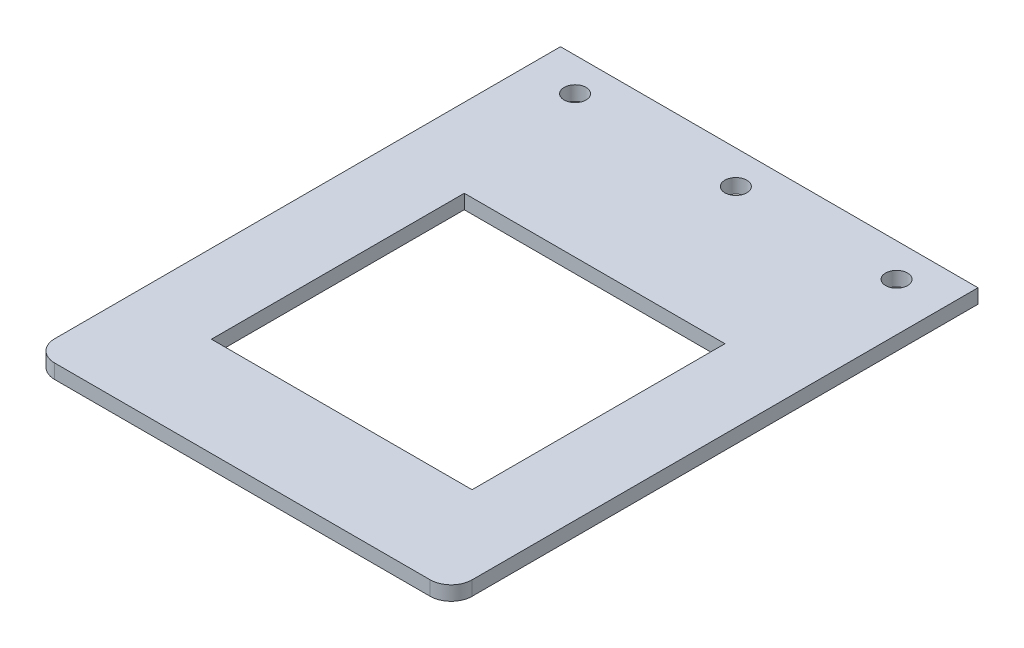
SolidWorks part; units mm, degrees
ref_plane "Front Plane" through (0, 0, 0) normal (0, 0, 1) x (1, 0, 0)
ref_plane "Top Plane" through (0, 0, 0) normal (0, 1, 0) x (1, 0, 0)
ref_plane "Right Plane" through (0, 0, 0) normal (1, 0, 0) x (0, 0, -1)
sketch "Sketch1" plane through (0, 0, 0) normal (0, 1, 0) x (1, 0, 0)
  line L10 (-16.9379, -16.3429) -> (10.3671, -16.3429)
  line L11 (10.3671, -16.3429) -> (10.3671, 10.1491)
  line L12 (10.3671, 10.1491) -> (-16.9379, 10.1491)
  line L13 (-16.9379, 10.1491) -> (-16.9379, -16.3429)
  line L16 (-14.2871, 14.6854) -> (12.9539, 14.6854)
  line L17 (12.9539, 14.6854) -> (12.9539, 18.4324)
  line L18 (12.9539, 18.4324) -> (-14.2871, 18.4324)
  line L19 (-14.2871, 18.4324) -> (-14.2871, 14.6854)
  line L22 (-25.1937, -23.3118) -> (-25.1937, 28.4832)
  line L23 (18.5453, 28.4832) -> (18.5453, -23.3118)
  line L24 (-25.1937, 28.4832) -> (18.5453, 28.4832)
  line L25 (18.5453, -23.3118) -> (18.5453, -24.5118)
  line L26 (-25.1937, -23.3118) -> (-25.1937, -24.5118)
  line L29 (16.3453, -26.7118) -> (-22.9937, -26.7118)
  circle A0 centre (-20.1649, 24.9832) radius 1.15
  circle A1 centre (-3.3249, 24.9832) radius 1.15
  circle A2 centre (13.5151, 24.9832) radius 1.15
  arc A5 (18.5453, -24.5118) -> (16.3453, -26.7118) centre (16.3453, -24.5118) cw
  arc A6 (-25.1937, -24.5118) -> (-22.9937, -26.7118) centre (-22.9937, -24.5118) ccw
extrude "Boss-Extrude1" add sketch "Sketch1" along normal blind 1.5
sketch "Sketch2" plane through (0, 1.5, 0) normal (0, 1, 0) x (1, 0, 0)
  line L0 (-14.2871, 18.4324) -> (12.9539, 18.4324)
  line L1 (12.9539, 18.4324) -> (12.9539, 14.6854)
  line L2 (12.9539, 14.6854) -> (-14.2871, 14.6854)
  line L3 (-14.2871, 14.6854) -> (-14.2871, 18.4324)
  line L4 (18.5453, 28.4832) -> (-25.1937, 28.4832)
  line L5 (-25.1937, 28.4832) -> (-25.1937, -24.5118)
  line L6 (-22.9937, -26.7118) -> (16.3453, -26.7118)
  line L7 (18.5453, -24.5118) -> (18.5453, 28.4832)
  line L8 (18.5453, 28.4832) -> (-25.1937, 28.4832)
  line L9 (-25.1937, 28.4832) -> (-25.1937, -24.5118)
  line L11 (18.5453, -24.5118) -> (18.5453, 28.4832)
  line L16 (-22.9937, -26.7118) -> (16.3453, -26.7118)
  arc A2 (-25.1937, -24.5118) -> (-22.9937, -26.7118) centre (-22.9937, -24.5118) ccw
  arc A3 (-25.1937, -24.5118) -> (-22.9937, -26.7118) centre (-22.9937, -24.5118) ccw
  arc A6 (16.3453, -26.7118) -> (18.5453, -24.5118) centre (16.3453, -24.5118) ccw
  arc A7 (16.3453, -26.7118) -> (18.5453, -24.5118) centre (16.3453, -24.5118) ccw
  dimension "D1" = 0
extrude "Boss-Extrude2" add sketch "Sketch2" along normal blind 2 separate body contours L3 L0 L1 L2
sketch "Sketch3" plane through (0, 1.5, 0) normal (0, -1, 0) x (1, 0, 0)
  line L4 (12.9539, -14.6854) -> (-14.2871, -14.6854)
  line L5 (-14.2871, -14.6854) -> (-14.2871, -18.4324)
  line L6 (-14.2871, -18.4324) -> (12.9539, -18.4324)
  line L7 (12.9539, -18.4324) -> (12.9539, -14.6854)
  line L8 (12.9539, -14.6854) -> (-14.2871, -14.6854)
  line L9 (-14.2871, -14.6854) -> (-14.2871, -18.4324)
  line L10 (-14.2871, -18.4324) -> (12.9539, -18.4324)
  line L11 (12.9539, -18.4324) -> (12.9539, -14.6854)
  dimension "D1" = 0
extrude "Boss-Extrude3" add sketch "Sketch3" along normal up to surface (1.5 mm away) up to face at (-3.3249, 0, -23.8332)
sketch "Sketch5" plane through (0, 0, 0) normal (0, -1, 0) x (1, 0, 0)
  line L0 (-14.2871, -18.4324) -> (-9.2871, -18.4324)
  line L1 (-9.2871, -18.4324) -> (-9.2871, -14.6854)
  line L2 (12.9539, -18.4324) -> (7.9539, -18.4324)
  line L3 (7.9539, -18.4324) -> (7.9539, -14.6854)
  line L4 (12.9539, -14.6854) -> (-14.2871, -14.6854)
  line L5 (12.9539, -18.4324) -> (12.9539, -14.6854)
  line L6 (-14.2871, -18.4324) -> (12.9539, -18.4324)
  line L7 (-14.2871, -14.6854) -> (-14.2871, -18.4324)
  line L8 (12.9539, -14.6854) -> (-14.2871, -14.6854)
  line L9 (12.9539, -18.4324) -> (12.9539, -14.6854)
  line L10 (-14.2871, -18.4324) -> (12.9539, -18.4324)
  line L11 (-14.2871, -14.6854) -> (-14.2871, -18.4324)
  line L12 (7.9539, -14.6854) -> (-9.2871, -14.6854)
  line L13 (-9.2871, -18.4324) -> (7.9539, -18.4324)
  dimension "D1" = 0
extrude "Boss-Extrude4" add sketch "Sketch5" along normal blind 2 contours L1 L10 L3 L8 region at (-0.6666, 0, -16.5589)
sketch "Sketch6" plane through (0, 3.5, 0) normal (0, 1, 0) x (1, 0, 0)
  line L4 (-14.2871, 14.6854) -> (12.9539, 14.6854)
  line L5 (12.9539, 14.6854) -> (12.9539, 18.4324)
  line L6 (12.9539, 18.4324) -> (-14.2871, 18.4324)
  line L7 (-14.2871, 18.4324) -> (-14.2871, 14.6854)
  line L8 (-14.2871, 14.6854) -> (12.9539, 14.6854)
  line L9 (12.9539, 14.6854) -> (12.9539, 18.4324)
  line L10 (12.9539, 18.4324) -> (-14.2871, 18.4324)
  line L11 (-14.2871, 18.4324) -> (-14.2871, 14.6854)
  dimension "D1" = 0
extrude "Cut-Extrude1" cut sketch "Sketch6" against normal up to surface (2 mm away) up to face at (-0.6666, 1.5, -16.5589)
